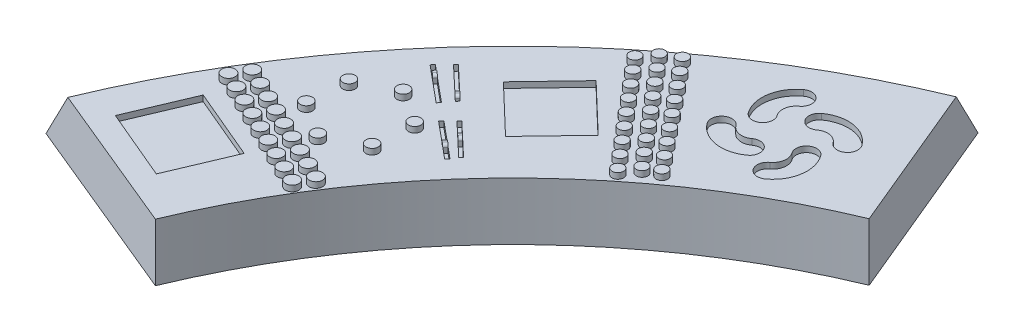
SolidWorks part; units mm, degrees
material "Alumina"
ref_plane "Front Plane" through (0, 0, 0) normal (0, 0, 1) x (1, 0, 0)
ref_plane "Top Plane" through (0, 0, 0) normal (0, 1, 0) x (1, 0, 0)
ref_plane "Right Plane" through (0, 0, 0) normal (1, 0, 0) x (0, 0, -1)
sketch "Sketch1" plane through (0, 0, 0) normal (0, 1, 0) x (1, 0, 0)
  line L0 (0, 1495.54) -> (0, -1495.54) construction
  line L1 (0, 0) -> (1057.5065, 1057.5065) construction
  line L2 (1057.5065, 1057.5065) -> (-1057.5065, -1057.5065) construction
  line L3 (-1057.5065, -1057.5065) -> (1057.5065, -1057.5065) construction
  line L4 (1057.5065, -1057.5065) -> (-1057.5065, 1057.5065) construction
  line L5 (-1057.5065, 1057.5065) -> (1057.5065, 1057.5065) construction
  line L6 (440.104, -1057.5065) -> (574.625, -1380.7411)
  line L7 (440.104, 1057.5065) -> (574.625, 1380.7411)
  line L8 (-440.104, 1057.5065) -> (-574.625, 1380.7411)
  line L9 (-440.104, -1057.5065) -> (-574.625, -1380.7411)
  line L10 (-1058.4838, 437.7482) -> (-1382.0172, 571.5491)
  circle A0 centre (0, 0) radius 1495.54
  arc A2 (440.104, 1057.5065) -> (440.104, -1057.5065) centre (0, 0) cw
  arc A3 (-440.104, -1057.5065) -> (-440.104, 1057.5065) centre (0, 0) cw
  arc A4 (-440.104, 1057.5065) -> (-1058.4838, 437.7482) centre (0, 0) ccw
extrude "Boss-Extrude1" add sketch "Sketch1" along normal blind 100 contours L10 A3 L8 A0 region at (-916.326, 0, -914.2879)
chamfer "Chamfer1" distance 100 angle 35 1 edges at (-1058.6832, 100, -1056.3285) first distance on face at (-1018.5021, 50, -1016.2368)
sketch "Sketch2" plane through (0, 100, 0) normal (0, 1, 0) x (1, 0, 0)
  line L0 (-1248.8423, 558.6772) -> (-1125.6399, 506.5387)
  line L1 (-1248.8423, 558.6772) -> (-1203.5398, 665.7263)
  line L2 (-1125.6399, 506.5387) -> (-1080.3374, 613.5878)
  line L3 (-1203.5398, 665.7263) -> (-1080.3374, 613.5878)
extrude "Cut-Extrude1" cut sketch "Sketch2" against normal blind 10
sketch "Sketch3" plane through (0, 100, 0) normal (0, 1, 0) x (1, 0, 0)
  circle A0 centre (-1204.8141, 710.8155) radius 11.5832
  circle A1 centre (-1177.8503, 697.6643) radius 11.5832
  circle A2 centre (-1150.8865, 684.5132) radius 11.5832
  circle A3 centre (-1123.9226, 671.3621) radius 11.5832
  circle A4 centre (-1096.9588, 658.2109) radius 11.5832
  circle A5 centre (-1069.995, 645.0598) radius 11.5832
  circle A6 centre (-1043.0312, 631.9086) radius 11.5832
  circle A7 centre (-1016.0674, 618.7575) radius 11.5832
  circle A8 centre (-989.1035, 605.6064) radius 11.5832
  circle A9 centre (-1162.3991, 723.3793) radius 11.5832
  circle A10 centre (-1135.4353, 710.2282) radius 11.5832
  circle A11 centre (-1108.4715, 697.0771) radius 11.5832
  circle A12 centre (-1081.5077, 683.9259) radius 11.5832
  circle A13 centre (-1054.5439, 670.7748) radius 11.5832
  circle A14 centre (-1027.58, 657.6237) radius 11.5832
  circle A15 centre (-1000.6162, 644.4725) radius 11.5832
  circle A16 centre (-973.6524, 631.3214) radius 11.5832
  circle A17 centre (-1189.363, 736.5305) radius 11.5832
  dimension "D1" = 9
  dimension "D2" = 2
extrude "Boss-Extrude2" add sketch "Sketch3" along normal blind 10
sketch "Sketch4" plane through (0, 100, 0) normal (0, 1, 0) x (1, 0, 0)
  circle A0 centre (-1091.3889, 806.406) radius 10.7258
  circle A1 centre (-1028.8581, 837.8685) radius 10.7258
  circle A2 centre (-970.3453, 799.4465) radius 10.7258
  circle A3 centre (-974.3634, 729.5619) radius 10.7258
  circle A4 centre (-1036.8942, 698.0994) radius 10.7258
  circle A5 centre (-1095.407, 736.5214) radius 10.7258
  dimension "D1" = 6
extrude "Boss-Extrude3" add sketch "Sketch4" along normal blind 10
sketch "Sketch5" plane through (0, 100, 0) normal (0, 1, 0) x (1, 0, 0)
  line L4 (-1052.1599, 907.8326) -> (-989.7445, 856.0222)
  line L5 (-1052.1599, 907.8326) -> (-1047.9864, 912.8604)
  line L6 (-989.7445, 856.0222) -> (-985.571, 861.05)
  line L7 (-1047.9864, 912.8604) -> (-985.571, 861.05)
  line L8 (-960.2346, 830.6981) -> (-897.8192, 778.8877)
  line L9 (-960.2346, 830.6981) -> (-956.061, 835.7259)
  line L10 (-956.061, 835.7259) -> (-893.6456, 783.9155)
  line L11 (-897.8192, 778.8877) -> (-893.6456, 783.9155)
  dimension "D1" = 2
extrude "Cut-Extrude2" cut sketch "Sketch5" against normal blind 10
sketch "Sketch6" plane through (0, 100, 0) normal (0, 1, 0) x (1, 0, 0)
  line L0 (-1032.0136, 928.4032) -> (-975.4146, 874.9307)
  line L1 (-1032.0136, 928.4032) -> (-1027.9251, 932.7307)
  line L2 (-975.4146, 874.9307) -> (-971.3261, 879.2583)
  line L3 (-1027.9251, 932.7307) -> (-971.3261, 879.2583)
  line L4 (-944.2512, 846.5634) -> (-887.6521, 793.0909)
  line L5 (-944.2512, 846.5634) -> (-940.1627, 850.8909)
  line L6 (-940.1627, 850.8909) -> (-883.5637, 797.4185)
  line L7 (-887.6521, 793.0909) -> (-883.5637, 797.4185)
  dimension "D1" = 2
extrude "Cut-Extrude3" cut sketch "Sketch6" against normal blind 10
sketch "Sketch7" plane through (0, 90, 0) normal (0, 1, 0) x (1, 0, 0)
  line L0 (-1038.2772, 897.0031) -> (-1034.4449, 901.6197)
  line L1 (-1038.2772, 897.0031) -> (-1030.7236, 890.7329)
  line L2 (-1034.4449, 901.6197) -> (-1026.8913, 895.3496)
  line L3 (-1030.7236, 890.7329) -> (-1026.8913, 895.3496)
  line L4 (-985.571, 861.05) -> (-1047.9864, 912.8604) construction
  dimension "D1" = 6
extrude "Boss-Extrude5" add sketch "Sketch7" along normal blind 14
fillet "Fillet2" radius 5 1 edges at (-1028.8074, 104, -893.0413)
sketch "Sketch8" plane through (0, 90, 0) normal (0, 1, 0) x (1, 0, 0)
  line L0 (-920.5471, 806.2461) -> (-924.8533, 801.0584)
  line L1 (-920.5471, 806.2461) -> (-913.2442, 800.1841)
  line L2 (-924.8533, 801.0584) -> (-917.5505, 794.9964)
  line L3 (-913.2442, 800.1841) -> (-917.5505, 794.9964)
  line L4 (-893.6456, 783.9155) -> (-956.061, 835.7259) construction
extrude "Boss-Extrude6" add sketch "Sketch8" along normal blind 14
fillet "Fillet3" radius 5 1 edges at (-915.3973, 104, -797.5902)
sketch "Sketch9" plane through (0, 90, 0) normal (0, 1, 0) x (1, 0, 0)
  line L0 (-917.4233, 829.4076) -> (-921.5117, 825.0801)
  line L1 (-917.4233, 829.4076) -> (-910.5466, 822.9109)
  line L2 (-921.5117, 825.0801) -> (-914.6351, 818.5833)
  line L3 (-910.5466, 822.9109) -> (-914.6351, 818.5833)
  line L4 (-883.5637, 797.4185) -> (-940.1627, 850.8909) construction
  line L5 (-944.2512, 846.5634) -> (-887.6521, 793.0909) construction
extrude "Boss-Extrude7" add sketch "Sketch9" along normal blind 14
fillet "Fillet4" radius 5 1 edges at (-912.5909, 104, -820.7471)
sketch "Sketch10" plane through (0, 90, 0) normal (0, 1, 0) x (1, 0, 0)
  line L0 (-982.9956, 890.2831) -> (-987.0841, 885.9556)
  line L1 (-982.9956, 890.2831) -> (-976.2545, 883.9144)
  line L2 (-987.0841, 885.9556) -> (-980.343, 879.5868)
  line L3 (-976.2545, 883.9144) -> (-980.343, 879.5868)
  line L4 (-971.3261, 879.2583) -> (-1027.9251, 932.7307) construction
  line L5 (-1032.0136, 928.4032) -> (-975.4146, 874.9307) construction
extrude "Boss-Extrude8" add sketch "Sketch10" along normal blind 14
fillet "Fillet5" radius 5 1 edges at (-978.2987, 104, -881.7506)
sketch "Sketch11" plane through (0, 100, 0) normal (0, 1, 0) x (1, 0, 0)
  line L0 (-962.9727, 945.8833) -> (-879.042, 865.6407)
  line L1 (-962.9727, 945.8833) -> (-884.4013, 1028.0659)
  line L2 (-879.042, 865.6407) -> (-800.4706, 947.8234)
  line L3 (-884.4013, 1028.0659) -> (-800.4706, 947.8234)
extrude "Cut-Extrude4" cut sketch "Sketch11" against normal blind 10
sketch "Sketch12" plane through (0, 100, 0) normal (0, 1, 0) x (1, 0, 0)
  circle A0 centre (-878.5926, 1089.6189) radius 10
  circle A1 centre (-859.309, 1066.6376) radius 10
  circle A2 centre (-840.0253, 1043.6563) radius 10
  circle A3 centre (-820.7417, 1020.6749) radius 10
  circle A4 centre (-801.4581, 997.6936) radius 10
  circle A5 centre (-782.1745, 974.7123) radius 10
  circle A6 centre (-762.8908, 951.7309) radius 10
  circle A7 centre (-743.6072, 928.7496) radius 10
  circle A8 centre (-724.3236, 905.7683) radius 10
  circle A9 centre (-841.2545, 1090.5967) radius 10
  circle A10 centre (-821.9709, 1067.6153) radius 10
  circle A11 centre (-802.6873, 1044.634) radius 10
  circle A12 centre (-783.4036, 1021.6527) radius 10
  circle A13 centre (-764.12, 998.6713) radius 10
  circle A14 centre (-744.8364, 975.69) radius 10
  circle A15 centre (-725.5527, 952.7087) radius 10
  circle A16 centre (-706.2691, 929.7273) radius 10
  circle A17 centre (-860.5381, 1113.578) radius 10
  dimension "D1" = 9
  dimension "D2" = 2
extrude "Boss-Extrude9" add sketch "Sketch12" along normal blind 10
sketch "Sketch13" plane through (0, 100, 0) normal (0, 1, 0) x (1, 0, 0)
  circle A0 centre (-835.2815, 1128.5572) radius 10
  circle A1 centre (-816.4019, 1105.2429) radius 10
  circle A2 centre (-797.5222, 1081.9285) radius 10
  circle A3 centre (-778.6426, 1058.6141) radius 10
  circle A4 centre (-759.763, 1035.2997) radius 10
  circle A5 centre (-740.8834, 1011.9853) radius 10
  circle A6 centre (-722.0038, 988.671) radius 10
  circle A7 centre (-703.1242, 965.3566) radius 10
  circle A8 centre (-684.2446, 942.0422) radius 10
  dimension "D1" = 9
extrude "Boss-Extrude10" add sketch "Sketch13" along normal blind 10
sketch "Sketch15" plane through (0, 100, 0) normal (0, 1, 0) x (1, 0, 0)
  arc A0 (-680.3009, 1180.1983) -> (-689.4622, 1122.1462) centre (-655.8555, 1146.5917) ccw construction
  arc A1 (-690.8221, 1194.6625) -> (-703.9263, 1111.6251) centre (-655.8555, 1146.5917) ccw
  arc A2 (-669.7798, 1165.7342) -> (-674.9981, 1132.6674) centre (-655.8555, 1146.5917) ccw
  arc A3 (-669.7798, 1165.7342) -> (-690.8221, 1194.6625) centre (-680.3009, 1180.1983) ccw
  arc A4 (-703.9263, 1111.6251) -> (-674.9981, 1132.6674) centre (-689.4622, 1122.1462) ccw
  arc A5 (-571.0392, 1150.8408) -> (-629.0913, 1160.0021) centre (-604.6458, 1126.3954) ccw construction
  arc A6 (-556.575, 1161.362) -> (-639.6124, 1174.4662) centre (-604.6458, 1126.3954) ccw
  arc A7 (-585.5033, 1140.3196) -> (-618.5701, 1145.538) centre (-604.6458, 1126.3954) ccw
  arc A8 (-585.5033, 1140.3196) -> (-556.575, 1161.362) centre (-571.0392, 1150.8408) ccw
  arc A9 (-639.6124, 1174.4662) -> (-618.5701, 1145.538) centre (-629.0913, 1160.0021) ccw
  arc A10 (-600.3967, 1041.579) -> (-591.2354, 1099.6311) centre (-624.8421, 1075.1857) ccw construction
  arc A11 (-589.8755, 1027.1149) -> (-576.7713, 1110.1523) centre (-624.8421, 1075.1857) ccw
  arc A12 (-610.9179, 1056.0432) -> (-605.6996, 1089.11) centre (-624.8421, 1075.1857) ccw
  arc A13 (-610.9179, 1056.0432) -> (-589.8755, 1027.1149) centre (-600.3967, 1041.579) ccw
  arc A14 (-576.7713, 1110.1523) -> (-605.6996, 1089.11) centre (-591.2354, 1099.6311) ccw
  arc A15 (-709.6585, 1070.9366) -> (-651.6064, 1061.7753) centre (-676.0518, 1095.382) ccw construction
  arc A16 (-724.1226, 1060.4154) -> (-641.0852, 1047.3112) centre (-676.0518, 1095.382) ccw
  arc A17 (-695.1944, 1081.4577) -> (-662.1275, 1076.2394) centre (-676.0518, 1095.382) ccw
  arc A18 (-695.1944, 1081.4577) -> (-724.1226, 1060.4154) centre (-709.6585, 1070.9366) ccw
  arc A19 (-641.0852, 1047.3112) -> (-662.1275, 1076.2394) centre (-651.6064, 1061.7753) ccw
  point P3 (-696.9046, 1153.0697)
  point P13 (-598.1679, 1167.4444)
  point P21 (-583.7931, 1068.7077)
  point P29 (-682.5298, 1054.333)
  dimension "D1" = 4
extrude "Cut-Extrude5" cut sketch "Sketch15" against normal blind 10
